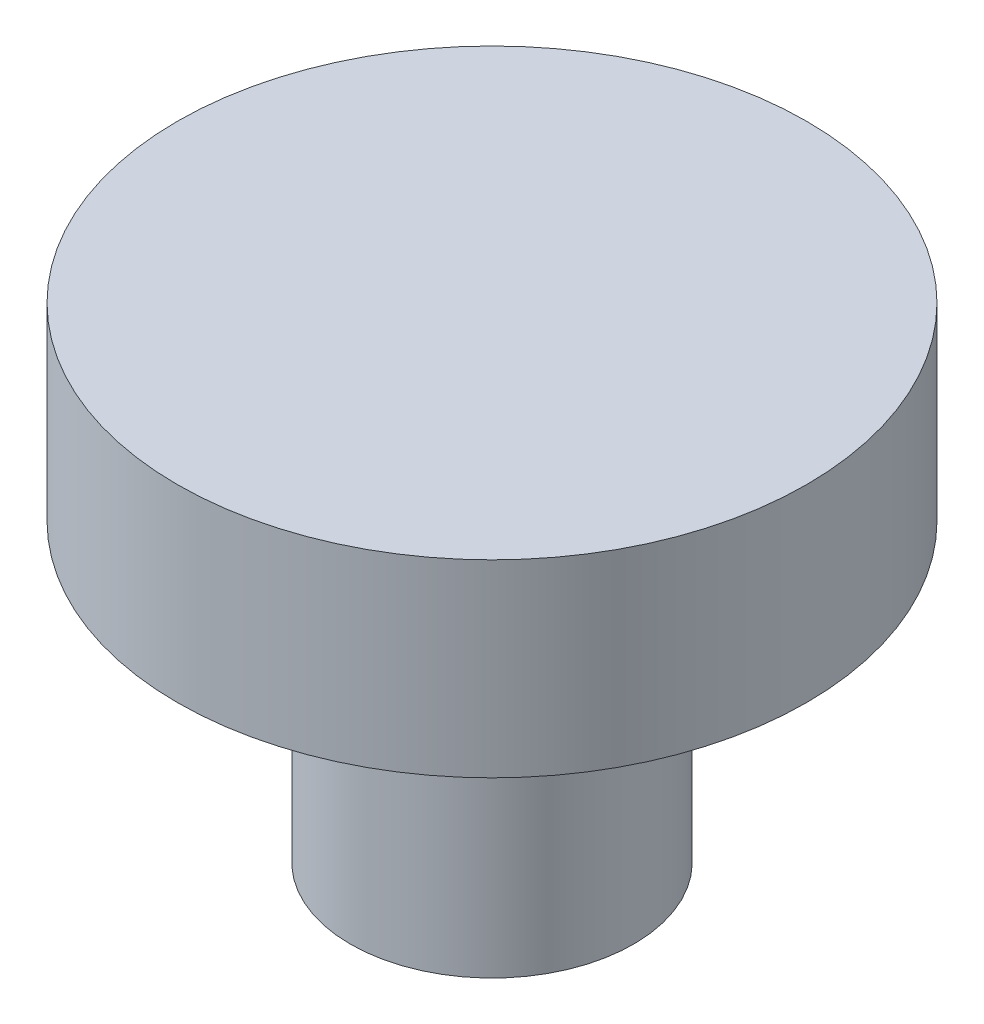
SolidWorks part; units mm, degrees
ref_plane "Front Plane" through (0, 0, 0) normal (0, 0, 1) x (1, 0, 0)
ref_plane "Top Plane" through (0, 0, 0) normal (0, 1, 0) x (1, 0, 0)
ref_plane "Right Plane" through (0, 0, 0) normal (1, 0, 0) x (0, 0, -1)
sketch "Sketch1" plane through (0, 0, 0) normal (1, 0, 0) x (0, 0, -1)
  line L0 (0, 0) -> (0, -47)
  line L1 (0, -47) -> (22.5, -47)
  line L2 (22.5, -47) -> (22.5, 0)
  line L3 (22.5, 0) -> (50, 0)
  line L4 (50, 0) -> (50, 30)
  line L5 (50, 30) -> (0, 30)
  line L6 (0, 30) -> (0, 0)
  dimension "D1" = 22.5
  dimension "D2" = 50
  dimension "D3" = 30
  dimension "D4" = 47
revolve "Revolve1" add sketch "Sketch1" angle 360 about L6
